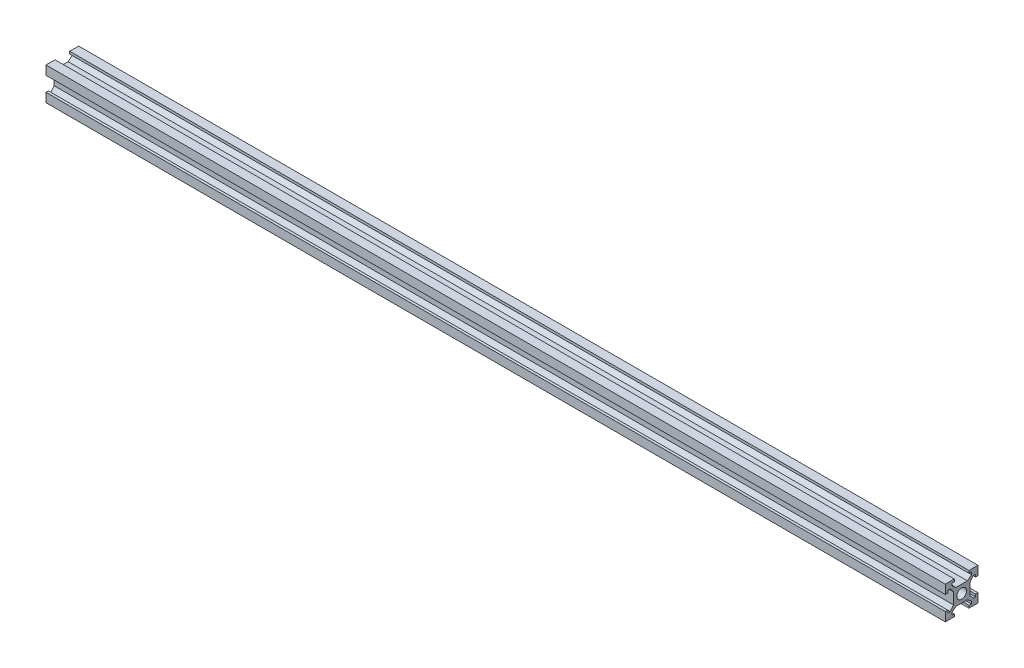
SolidWorks part; units mm, degrees
ref_plane "Front Plane" through (0, 0, 0) normal (0, 0, 1) x (1, 0, 0)
ref_plane "Top Plane" through (0, 0, 0) normal (0, 1, 0) x (1, 0, 0)
ref_plane "Right Plane" through (0, 0, 0) normal (1, 0, 0) x (0, 0, -1)
sketch "Sketch1" plane through (0, 0, 0) normal (1, 0, 0) x (0, 0, -1)
  line L1 (-10, 10) -> (10, 10)
  line L2 (-10, 10) -> (-10, -10)
  line L3 (-10, -10) -> (10, -10)
  line L4 (10, 10) -> (10, -10)
  line L5 (-10, 10) -> (10, -10) construction
  line L6 (-10, -10) -> (10, 10) construction
  point P0 (0, 0)
  dimension "D1" = 20
  dimension "D2" = 20
extrude "Boss-Extrude1" add sketch "Sketch1" along normal blind 550
sketch "Sketch2" plane through (550, 0, 0) normal (1, 0, 0) x (0, 0, -1)
  line L0 (0, 0) -> (0, 10) construction
  line L1 (10, 10) -> (-10, 10) construction
  line L2 (-4.5, 10) -> (-4.5, 8.5)
  line L3 (-4.5, 8.5) -> (-6, 8.5)
  line L4 (-6, 8.5) -> (-6, 7)
  line L5 (-6, 7) -> (-3.5, 5)
  line L6 (-3.5, 5) -> (3.5, 5)
  line L7 (-4.5, 10) -> (4.5, 10)
  line L8 (6, 7) -> (3.5, 5)
  line L9 (6, 8.5) -> (6, 7)
  line L10 (4.5, 8.5) -> (6, 8.5)
  line L11 (4.5, 10) -> (4.5, 8.5)
  circle A0 centre (0, 0) radius 3
  point P14 (0, 5)
  line M2 (10, 10) -> (-10, 10)
  dimension "D1" = 6
  dimension "D2" = 4.5
  dimension "D3" = 3.5
  dimension "D4" = 1.5
  dimension "D5" = 1.5
  dimension "D6" = 2
extrude "Cut-Extrude1" cut sketch "Sketch2" against normal through all contours A0 region at (550, 0, 0)
extrude "Cut-Extrude2" cut sketch "Sketch2<3>" against normal through all contours L0 L6 L8 L9 L10 L11 M2 | L6 L0 L7 L2 L3 L4 L5 region at (550, 7.5256, 2.585) region at (550, 7.5256, -2.585)
sketch "Sketch2<3>" plane through (550, 0, 0) normal (1, 0, 0) x (0, 0, -1) same geometry as "Sketch2"
pattern_circular "CirPattern1" count 4 every 90 about axis through (0, 0, 0) along (1, 0, 0) of "Cut-Extrude2"
